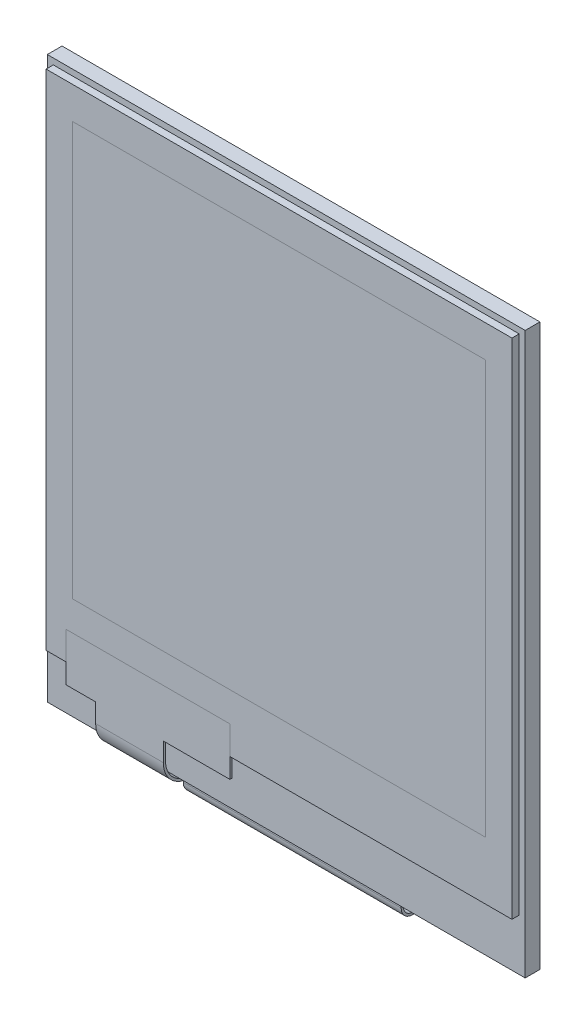
SolidWorks part; units mm, degrees
ref_plane "Front Plane" through (0, 0, 0) normal (0, 0, 1) x (1, 0, 0)
ref_plane "Top Plane" through (0, 0, 0) normal (0, 1, 0) x (1, 0, 0)
ref_plane "Right Plane" through (0, 0, 0) normal (1, 0, 0) x (0, 0, -1)
sketch "Sketch1" plane through (0, 0, 0) normal (0, 0, 1) x (1, 0, 0)
  line L1 (-15.9, 18.66) -> (15.9, 18.66)
  line L2 (-15.9, 18.66) -> (-15.9, -18.66)
  line L3 (-15.9, -18.66) -> (15.9, -18.66)
  line L4 (15.9, 18.66) -> (15.9, -18.66)
  line L5 (-15.9, 18.66) -> (15.9, -18.66) construction
  line L6 (-15.9, -18.66) -> (15.9, 18.66) construction
  point P0 (0, 0)
  dimension "D1" = 31.8
  dimension "D2" = 37.32
extrude "Boss-Extrude1" add sketch "Sketch1" along normal blind 0.98
sketch "Sketch2" plane through (0, 0, 0.98) normal (0, 0, 1) x (1, 0, 0)
  line L0 (0, 18.26) -> (0, 1.0637)
  line L1 (-15.5, 18.26) -> (15.5, 18.26)
  line L2 (-15.5, 18.26) -> (-15.5, -15.24)
  line L3 (-15.5, -15.24) -> (15.5, -15.24)
  line L4 (15.5, 18.26) -> (15.5, -15.24)
  line L5 (15.9, 18.66) -> (-15.9, 18.66) construction
  dimension "D1" = 31
  dimension "D2" = 33.5
  dimension "D3" = 0.4
extrude "Boss-Extrude2" add sketch "Sketch2" along normal blind 1.46 from surface contours L4 L1 L2 L3 region at (-7.75, 17.8036, 0.98) starting at face at (0, 0, 0)
sketch "Sketch3" plane through (0, 0, 1.46) normal (0, 0, 1) x (1, 0, 0)
  line L0 (-14.17, -15.24) -> (-14.17, -16.56)
  line L1 (15.5, -15.24) -> (-15.5, -15.24) construction
  line L2 (-14.17, -16.56) -> (-12.2, -16.56)
  line L3 (-12.2, -16.56) -> (-12.2, -17.06)
  line L4 (-12.2, -17.06) -> (-7.7, -17.06)
  line L5 (-7.7, -17.06) -> (-7.7, -16.56)
  line L6 (-7.7, -16.56) -> (-3.27, -16.56)
  line L7 (-3.27, -16.56) -> (-3.27, -15.24)
  line L8 (-15.5, -15.24) -> (15.5, -15.24) construction
  line L9 (-15.5, -15.24) -> (-15.5, 18.26) construction
  line L10 (-15.9, 18.66) -> (-15.9, -18.66) construction
  line L11 (-15.9, -18.66) -> (15.9, -18.66) construction
  line L12 (-14.17, -15.24) -> (-3.27, -15.24)
  dimension "D1" = 10.9
  dimension "D2" = 1.33
  dimension "D3" = 3.7
  dimension "D4" = 4.5
  dimension "D5" = 2.1
  dimension "D6" = 0.5
extrude "Boss-Extrude3" add sketch "Sketch3" against normal blind 0.15
sketch "Sketch4" plane through (0, 0, 0.98) normal (0, 0, 1) x (1, 0, 0)
  line L0 (-15.9, -18.66) -> (15.9, -18.66) construction
  line L1 (-7.25, -18.66) -> (7.25, -18.66)
  line L2 (-7.25, -18.66) -> (-7.25, -19.16)
  line L3 (-7.25, -19.16) -> (7.25, -19.16)
  line L4 (7.25, -18.66) -> (7.25, -19.16)
  line L5 (0, -18.66) -> (0, 0) construction
  dimension "D1" = 14.5
  dimension "D2" = 0.5
extrude "Boss-Extrude4" add sketch "Sketch4" against normal blind 0.15 from offset 0.4 contours L2 L1 L4 L3 offset against normal yes
sketch "Sketch5" plane through (0, 0, 1.46) normal (0, 0, 1) x (1, 0, 0)
  line L0 (0, 2.365) -> (0, 0) construction
  line L1 (13.755, -11.39) -> (-13.755, -11.39)
  line L2 (13.755, -11.39) -> (13.755, 16.12)
  line L3 (13.755, 16.12) -> (-13.755, 16.12)
  line L4 (-13.755, -11.39) -> (-13.755, 16.12)
  line L5 (13.755, -11.39) -> (-13.755, 16.12) construction
  line L6 (13.755, 16.12) -> (-13.755, -11.39) construction
  line L7 (15.5, 18.26) -> (-15.5, 18.26) construction
  point P0 (0, 2.365)
  dimension "D1" = 27.51
  dimension "D2" = 2.14
wrap "Wrap1" sketch "Sketch5" wrap type scribe source sketch "Sketch5"
sketch "Sketch6" plane through (0, 0, 1.46) normal (0, 0, 1) x (1, 0, 0)
  line L0 (-14.17, -15.24) -> (-14.17, -13.36)
  line L1 (-14.17, -13.36) -> (-3.27, -13.36)
  line L2 (-3.27, -13.36) -> (-3.27, -15.24)
  line L3 (-3.27, -16.56) -> (-3.27, -15.24) construction
  line L4 (-7.7, -16.56) -> (-3.27, -16.56) construction
  line L5 (-7.7, -17.06) -> (-7.7, -16.56) construction
  line L6 (-12.2, -17.06) -> (-7.7, -17.06) construction
  line L7 (-12.2, -16.56) -> (-12.2, -17.06) construction
  line L8 (-14.17, -16.56) -> (-12.2, -16.56) construction
  line L9 (-14.17, -15.24) -> (-14.17, -16.56) construction
  line L10 (-3.27, -16.56) -> (-3.27, -15.24)
  line L11 (-7.7, -16.56) -> (-3.27, -16.56)
  line L12 (-7.7, -17.06) -> (-7.7, -16.56)
  line L13 (-12.2, -17.06) -> (-7.7, -17.06)
  line L14 (-12.2, -16.56) -> (-12.2, -17.06)
  line L15 (-14.17, -16.56) -> (-12.2, -16.56)
  line L16 (-14.17, -15.24) -> (-14.17, -16.56)
  dimension "D1" = 3.2
wrap "Wrap2" sketch "Sketch6" wrap type scribe source sketch "Sketch6"
sketch "Sketch7" plane through (-12.2, 0, 0) normal (-1, 0, 0) x (0, 0, 1)
  line L0 (1.46, -17.06) -> (1.46, -17.81)
  line L1 (-2.04, -17.81) -> (-2.04, -17.31)
  line L2 (0.98, -18.66) -> (0, -18.66) construction
  arc A0 (1.46, -17.81) -> (-2.04, -17.81) centre (-0.29, -17.81) cw
  point P5 (-1.5983, -16.9733)
  point P7 (0, 0)
  point P8 (-1.5948, -19.4193)
  dimension "D2" = 1.75
  dimension "D1" = 0.75
  dimension "D3" = 1.35
extrude "Extrude-Thin1" add sketch "Sketch7" against normal up to surface (4.5 mm away) thin thin type one direction wall 0.15
sketch "Sketch8" plane through (0, 0, -2.04) normal (0, 0, -1) x (-1, 0, 0)
  line L0 (7.7, -17.31) -> (7.7, -11.31)
  line L1 (7.7, -11.31) -> (9.7, -11.31)
  line L2 (9.7, -11.31) -> (9.7, -8.81)
  line L3 (9.7, -8.81) -> (12.2, -8.81)
  line L4 (12.2, -8.81) -> (12.2, -3.81)
  line L6 (12.2, -3.81) -> (15.7, -3.81)
  line L7 (15.7, -3.81) -> (15.7, -8.81)
  line L8 (15.7, -8.81) -> (18.2, -8.81)
  line L9 (18.2, -8.81) -> (18.2, -15.01)
  line L10 (18.2, -15.01) -> (16.2, -15.01)
  line L11 (16.2, -15.01) -> (16.2, -17.31)
  line L12 (16.2, -17.31) -> (7.7, -17.31)
  dimension "D1" = 8.5
  dimension "D2" = 10.5
  dimension "D3" = 2.3
  dimension "D4" = 6
  dimension "D5" = 8.5
  dimension "D6" = 8.5
  dimension "D7" = 2.5
  dimension "D8" = 3.5
  dimension "D9" = 13.5
extrude "Boss-Extrude6" add sketch "Sketch8" against normal blind 0.15 contours L12 L0 L1 L2 L3 L4 L6 L7 L8 L9 L10 L11
ref_plane "Plane1" through (-7.25, -18.66, 0.43) normal (0, -1, 0) x (-1, 0, 0)
sketch "Sketch10" plane through (-7.25, 0, 0) normal (-1, 0, 0) x (0, 0, 1)
  line L0 (-2.04, -11.1498) -> (-2.04, -7.66)
  line L1 (0.98, -18.66) -> (0, -18.66) construction
  line L2 (-2.04, -15.01) -> (-2.04, -17.31) construction
  arc A0 (0.58, -19.16) -> (-0.8913, -19.372) centre (-0.17, -19.1665) cw
  arc A1 (-0.8913, -19.372) -> (-2.04, -11.1498) centre (27.96, -11.1498) cw
  dimension "D1" = 0.75
  dimension "D2" = 30
  dimension "D3" = 11
extrude "Extrude-Thin2" add sketch "Sketch10" against normal up to surface (14.5 mm away) separate body thin up to face at (7.25, -18.91, 0.505) thin type one direction wall 0.15
sketch "Sketch11" plane through (0, 0, -2.04) normal (0, 0, -1) x (-1, 0, 0)
  line L1 (-7.25, -7.66) -> (-5.25, -7.66)
  line L2 (-7.25, -7.66) -> (-7.25, -15.66)
  line L3 (-7.25, -15.66) -> (-5.25, -15.66)
  line L4 (-5.25, -7.66) -> (-5.25, -15.66)
  line L5 (7.25, -7.66) -> (5.25, -7.66)
  line L6 (7.25, -7.66) -> (7.25, -15.66)
  line L7 (7.25, -15.66) -> (5.25, -15.66)
  line L8 (5.25, -7.66) -> (5.25, -15.66)
  dimension "D1" = 10.5
  dimension "D2" = 8
extrude "Boss-Extrude7" add sketch "Sketch11" against normal up to next contours L2 L1 L4 L3 | L6 L5 L8 L7
